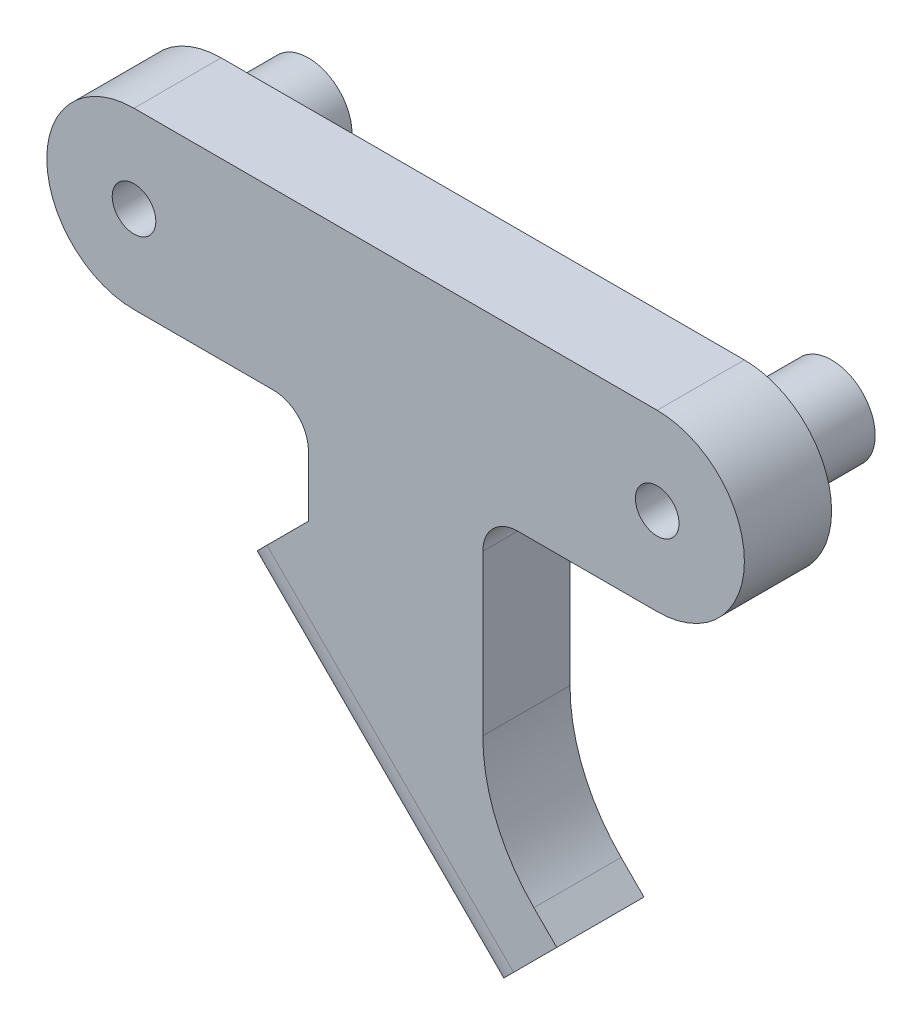
SolidWorks part; units mm, degrees
material "PET"
ref_plane "Piano frontale" through (0, 0, 0) normal (0, 0, 1) x (1, 0, 0)
ref_plane "Piano superiore" through (0, 0, 0) normal (0, 1, 0) x (1, 0, 0)
ref_plane "Piano destro" through (0, 0, 0) normal (1, 0, 0) x (0, 0, -1)
sketch "Schizzo1" plane through (0, 0, 0) normal (0, 0, 1) x (1, 0, 0)
  line L1 (-13.208, 5) -> (16.792, 5)
  line L2 (-13.208, -5) -> (-3.208, -5)
  line L3 (6.792, -28.7941) -> (6.792, -18.7941)
  line L4 (-3.208, -18.7941) -> (6.792, -28.7941)
  line L5 (6.792, -5) -> (16.792, -5)
  line L7 (-3.208, -5) -> (-3.208, -18.7941)
  line L9 (6.792, -5) -> (6.792, -18.7941)
  line L10 (6.792, 0) -> (16.792, 0) construction
  arc A0 (-13.208, 5) -> (-13.208, -5) centre (-13.208, 0) ccw
  arc A1 (16.792, -5) -> (16.792, 5) centre (16.792, 0) ccw
  point P3 (1.792, 0)
  dimension "D1" = 30
  dimension "D2" = 10
  dimension "D3" = 10
  dimension "D4" = 10
extrude "Estrusione-Estrusione3" add sketch "Schizzo1" along normal blind 5 contours L2 L7 L4 L3 L9 L5 A1 L1 A0
sketch "Schizzo3" plane through (0, 0, 0) normal (0, 0, -1) x (-1, 0, 0)
  line L6 (13.208, 5) -> (-16.792, 5)
  line L7 (-16.792, -5) -> (-6.792, -5)
  line L8 (-6.792, -5) -> (-6.792, -28.7941)
  line L9 (-6.792, -28.7941) -> (3.208, -18.7941)
  line L10 (3.208, -18.7941) -> (3.208, -5)
  line L11 (3.208, -5) -> (13.208, -5)
  line L12 (13.208, 5) -> (-16.792, 5) construction
  line L13 (-16.792, -5) -> (-6.792, -5) construction
  line L14 (-6.792, -5) -> (-6.792, -28.7941) construction
  line L15 (-6.792, -28.7941) -> (3.208, -18.7941) construction
  line L16 (3.208, -18.7941) -> (3.208, -5) construction
  line L17 (3.208, -5) -> (13.208, -5) construction
  circle A0 centre (-16.792, 0) radius 2.5
  circle A1 centre (13.208, 0) radius 2.5
  arc A2 (13.208, -5) -> (13.208, 5) centre (13.208, 0) ccw
  arc A3 (-16.792, 5) -> (-16.792, -5) centre (-16.792, 0) ccw
  arc A4 (13.208, -5) -> (13.208, 5) centre (13.208, 0) ccw construction
  arc A5 (-16.792, 5) -> (-16.792, -5) centre (-16.792, 0) ccw construction
  dimension "D1" = 0
extrude "Estrusione-Estrusione4" add sketch "Schizzo3" along normal blind 5
ref_plane "Piano1" through (17.7931, -17.7931, 0) normal (-0.7071, 0.7071, 0) x (0, 0, -1)
sketch "Schizzo7" plane through (17.7931, -17.7931, 0) normal (-0.7071, 0.7071, 0) x (0, 0, -1)
  line L0 (-5, 15.5578) -> (-5, -1.2671) construction
  line L1 (0, 15.5578) -> (-5, 15.5578)
  line L2 (0, 15.5578) -> (0, 9.5578)
  line L3 (0, 9.5578) -> (-5, 9.5578)
  line L4 (-5, 15.5578) -> (-5, 9.5578)
  dimension "D1" = 6
extrude "Estrusione-Estrusione5" add sketch "Schizzo7" along normal blind 20
sketch "Schizzo6" plane through (17.7931, -17.7931, 0) normal (-0.7071, 0.7071, 0) x (0, 0, -1)
  line L0 (0, -1.2671) -> (0, 9.5578) construction
  line L1 (-5, 15.5578) -> (0, 15.5578) construction
  circle A0 centre (-2.5, 12.5578) radius 1.65
  dimension "D1" = 3.3
  dimension "D2" = 2.5
  dimension "D3" = 3
extrude "Taglio-Estrusione1" cut sketch "Schizzo6" along normal up to surface (20 mm away) up to face at (-5.2791, -12.5809, 2.5)
fillet "Raccordo1" radius 2.5 2 edges at (-0.2791, -21.723, 0) (-0.2791, -21.723, 5)
sketch "Schizzo8" plane through (0, 0, -5) normal (0, 0, -1) x (-1, 0, 0)
  circle A0 centre (-16.792, 0) radius 1.25
  circle A1 centre (13.208, 0) radius 1.25
  dimension "D1" = 2.5
extrude "Taglio-Estrusione2" cut sketch "Schizzo8" against normal through all
fillet "Raccordo2" radius 2 2 edges at (-3.208, -5, 2.5) (6.792, -5, 2.5)
fillet "Raccordo3" radius 10 1 edges at (6.792, -20.3088, 2.5)
ref_axis "Assi1" through (-5.2288, -12.5306, 2.5) along (0.7071, -0.7071, 0)
ref_point "Punto1"
ref_axis "Assi2" through (11.0346, -24.5515, 5) along (0, 0, -1)
ref_point "Punto2"
ref_axis "Assi3" through (16.792, 0, 5) along (0, 0, -1)
ref_axis "Assi4" through (6.792, -7, 0) along (0, -1, 0)
ref_point "Punto3"
sketch "Schizzo9" plane through (0, 0, 0) normal (0, 0, -1) x (-1, 0, 0)
  line L0 (-16.792, 0) -> (13.208, 0)
  line L1 (-1.792, 0) -> (-1.792, -20.2586)
  line L2 (-8.5598, -27.0263) -> (5.5824, -12.8842) construction
  point P4 (-1.792, 0)
